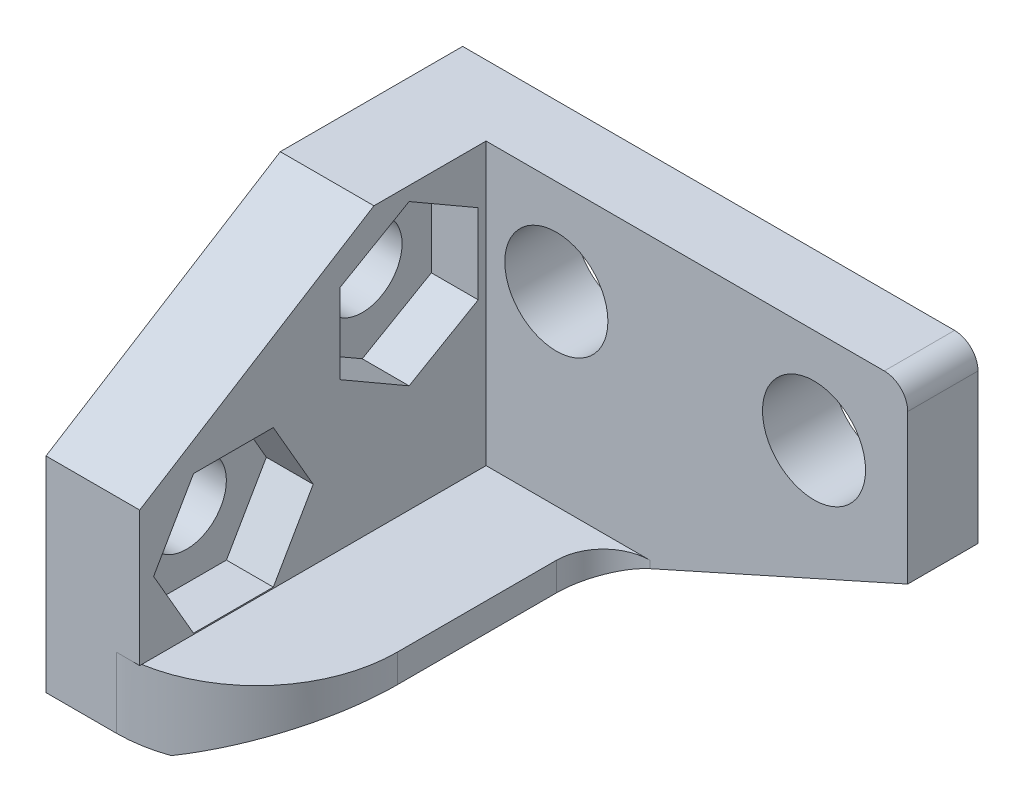
SolidWorks part; units mm, degrees
ref_plane "Спереди" through (0, 0, 0) normal (0, 0, 1) x (1, 0, 0)
ref_plane "Сверху" through (0, 0, 0) normal (0, 1, 0) x (1, 0, 0)
ref_plane "Справа" through (0, 0, 0) normal (1, 0, 0) x (0, 0, -1)
sketch "Эскиз1" plane through (0, 0, 0) normal (0, 0, 1) x (1, 0, 0)
  line L1 (-20, 25) -> (20, 25)
  line L2 (-20, 25) -> (-20, -25)
  line L3 (-20, -25) -> (20, -25)
  line L4 (20, 25) -> (20, -25)
  line L5 (-20, 25) -> (20, -25) construction
  line L6 (-20, -25) -> (20, 25) construction
  point P0 (0, 0)
  dimension "D1" = 50
  dimension "D2" = 40
extrude "Бобышка-Вытянуть1" add sketch "Эскиз1" along normal blind 5
sketch "Эскиз5" plane through (0, 0, 5) normal (0, 0, 1) x (1, 0, 0)
  line L0 (-20, 25) -> (-12.6319, 25)
  line L1 (-12.6319, 25) -> (-12.6319, 16.8645)
  line L2 (-12.6319, 16.8645) -> (13.9785, 16.8645)
  line L3 (13.9785, 16.8645) -> (14, 11)
  line L4 (14, 11) -> (-15, -2)
  line L5 (-15, -2) -> (-20, -2)
  line L6 (-20, -2) -> (-20, 25)
  line L7 (-12.6319, 25) -> (20, 25)
  line L8 (20, 25) -> (20, -25)
  line L9 (20, -25) -> (-20, -25)
  line L10 (-20, -25) -> (-20, -2)
  line M1 (20, -25) -> (20, 25)
  line M2 (20, 25) -> (-20, 25)
  line M3 (-20, 25) -> (-20, -25)
  line M4 (-20, -25) -> (20, -25)
extrude "Вырез-Вытянуть2" cut sketch "Эскиз5" against normal through all contours L4 L5 L1 L2 L3 M3 M4 M1 M2 region at (2.5012, -3.7526, 5)
fillet "Скругление2" radius 3 1 edges at (-12.6319, 16.8645, 2.5)
sketch "Эскиз6" plane through (0, 0, 5) normal (0, 0, 1) x (1, 0, 0)
  line L0 (-20, 25) -> (-17, 25)
  line L1 (-12.6319, 25) -> (-20, 25) construction
  line L2 (-17, 25) -> (-17, -2)
  line L3 (-15, -2) -> (-20, -2) construction
  line L4 (-17, -2) -> (-20, -2)
  line L5 (-20, -2) -> (-20, 25)
  line L6 (-17, -2) -> (-15, -2)
  line L7 (-15, -2) -> (-15, 1)
  line L8 (-15, 1) -> (-17, 1)
  line M4 (-12.6319, 25) -> (-20, 25)
  line M5 (-20, 25) -> (-20, -2)
  line M6 (-20, -2) -> (-15, -2)
  dimension "D1" = 3
  dimension "D2" = 3
extrude "Бобышка-Вытянуть2" add sketch "Эскиз6" along normal blind 10 contours L2 M4 M5 M6 | L7 L8 L2 M6 region at (-18.5, 11.5, 5) region at (-16, -0.5, 5)
sketch "Эскиз8" plane through (0, 0, 5) normal (0, 0, 1) x (1, 0, 0)
  line L0 (13.9785, 16.8645) -> (2.9785, 16.8645)
  line L1 (-9.6319, 16.8645) -> (13.9785, 16.8645) construction
  line L2 (2.9785, 16.8645) -> (2.9785, 6.0593)
  line L3 (14, 11) -> (-15, -2) construction
  line L4 (2.9785, 6.0593) -> (14, 11)
  line L5 (14, 11) -> (13.9785, 16.8645)
  dimension "D1" = 11
extrude "Вырез-Вытянуть3" cut sketch "Эскиз8" against normal through all
sketch "Эскиз9" plane through (0, 0, 5) normal (0, 0, 1) x (1, 0, 0)
  line L0 (-9.6319, 16.8645) -> (-20, 16.8645)
  line L1 (-20, 25) -> (-20, -2) construction
  line L2 (-20, 16.8645) -> (-20, 25)
  line L3 (-20, 25) -> (-9.6319, 25)
  line L4 (-9.6319, 25) -> (-9.6319, 16.8645)
extrude "Вырез-Вытянуть4" cut sketch "Эскиз9" against normal through all
sketch "Эскиз10" plane through (0, 0, 5) normal (0, 0, -1) x (-1, 0, 0)
  line L0 (17, 16.8645) -> (17, 25)
  line L1 (17, 25) -> (20, 25)
  line L2 (20, 25) -> (20, 16.8645)
  line L3 (20, 16.8645) -> (17, 16.8645)
  line L4 (17, 16.8645) -> (16.9146, 16.7365)
  line M1 (17, 16.8645) -> (20, 16.8645)
  line M2 (20, 16.8645) -> (20, 25)
  line M3 (20, 25) -> (17, 25)
  line M4 (17, 25) -> (17, 16.8645)
extrude "Вырез-Вытянуть5" cut sketch "Эскиз10" against normal through all contours M4 M1 M2 M3 region at (-18.5, 20.9323, 5)
fillet "Скругление3" radius 4 1 edges at (2.9785, 16.8645, 2.5)
fillet "Скругление4" radius 4 1 edges at (-15, -0.5, 5)
fillet "Скругление5" radius 4 1 edges at (-15, -0.5, 15)
sketch "Эскиз11" plane through (0, 0, 5) normal (0, 0, 1) x (1, 0, 0)
  line L0 (-17, 8.9323) -> (-21.0837, 8.9323) construction
  line L3 (-17, 16.8645) -> (-17, 1) construction
  line L4 (-21.0837, 8.9323) -> (5.5984, 8.9323) construction
  line L5 (-20, 8.9323) -> (-13, 8.9323)
  line L6 (-13, 8.9323) -> (-2, 8.9323)
  line L7 (-2, 8.9323) -> (2.879, 8.9323)
  circle A0 centre (-13, 8.9323) radius 2
  circle A1 centre (-2, 8.9323) radius 2
  dimension "D1" = 4
  dimension "D2" = 7
  dimension "D3" = 11
sketch "Эскиз12" plane through (-17, 0, 0) normal (1, 0, 0) x (0, 0, -1)
  line L0 (-9.7321, 16.8645) -> (-9.7321, 5.3907)
  line L1 (-14.4641, 16.8645) -> (-5, 16.8645) construction
  line L2 (-9.7321, 5.3907) -> (-15.9014, 5.3907)
  line L3 (-15.9014, 5.3907) -> (-15.9014, 16.8645)
  line L4 (-15.9014, 16.8645) -> (-9.7321, 16.8645)
extrude "Вырез-Вытянуть6" cut sketch "Эскиз12" against normal through all
sketch "Эскиз15" plane through (-20, 0, 0) normal (-1, 0, 0) x (0, 0, 1)
  line L0 (0, -2) -> (0, 13)
  line L1 (0, 16.8645) -> (0, -2) construction
  line L2 (0, 13) -> (9.7321, 13)
  line L3 (9.7321, 5.3907) -> (9.7321, 16.8645) construction
  line L4 (9.7321, 13) -> (9.7321, 16.8645)
  line L5 (9.7321, 16.8645) -> (0, 16.8645)
  line L6 (0, 16.8645) -> (0, 13)
  line M5 (9.7321, 5.3907) -> (9.7321, 16.8645)
  line M6 (9.7321, 16.8645) -> (0, 16.8645)
  line M7 (0, 16.8645) -> (0, -2)
  dimension "D1" = 15
extrude "Вырез-Вытянуть8" cut sketch "Эскиз15" against normal through all contours L2 M7 M5 M6 region at (-20, 14.9323, 4.866)
fillet "Скругление6" radius 8 1 edges at (-18.5, 5.3907, 9.7321)
fillet "Скругление7" radius 1 1 edges at (-18.5, 13, 9.7321)
sketch "Эскиз16" plane through (0, 0, 0) normal (0, 0, -1) x (-1, 0, 0)
  line L0 (20, 13) -> (-2, 13)
  line L1 (-2.9762, 13) -> (20, 13) construction
  line L2 (-2, 13) -> (-2, 2.1922)
  line L5 (0, 4.7241) -> (15, -2)
  line L7 (-2, 2.1922) -> (-7.7664, 2.1922)
  line L8 (-7.7664, 2.1922) -> (-7.7664, 13)
  line L9 (-7.7664, 13) -> (-2, 13)
  line M3 (20, 13) -> (-2.9762, 13)
  arc M4 (-2.9762, 13) -> (-2.9785, 12.8645) centre (1.0215, 12.8645) ccw
  line M5 (-2.9785, 12.8645) -> (-2.9785, 6.0593)
  line M6 (-2.9785, 6.0593) -> (15, -2)
  dimension "D1" = 22
extrude "Вырез-Вытянуть12" cut sketch "Эскиз16" against normal blind 10 contours L9 L8 L7 L2 M6 M5 M4 | L2 M3 M4 M5 M6 region at (2.4843, 9.4188, 0) region at (5.187, 7.3652, 0)
fillet "Скругление8" radius 1 1 edges at (2, 13, 2.5)
extrude "Вырез-Вытянуть13" cut sketch "Эскиз11" against normal blind 10 contours L5 A0 L6 | L6 A0 L5 | L6 A1 L7 | L7 A1 L6 region at (-13, 9.7811, 5) region at (-2, 9.7811, 5) region at (-2, 8.0834, 5) region at (-13, 8.0834, 5)
sketch "Эскиз18" plane through (-17, 0, 0) normal (1, 0, 0) x (0, 0, -1)
  line L0 (-5, 13) -> (-15.7866, 13)
  line L1 (-15.7866, 13) -> (-15.7866, -2)
  line L2 (-15.7866, -2) -> (-9, -2)
  line L3 (-11, -2) -> (-9, -2) construction
  line L4 (-5, 13) -> (-5, -2)
  line L5 (0, -2) -> (-9, -2) construction
  line L6 (-5, -2) -> (-9, -2)
extrude "Бобышка-Вытянуть3" add sketch "Эскиз18" against normal blind 3
sketch "Эскиз19" plane through (-17, 0, 0) normal (1, 0, 0) x (0, 0, -1)
  line L0 (-15.7866, 13) -> (-8.2866, 13)
  line L1 (-15.7866, 13) -> (-5, 13) construction
  line L2 (-8.2866, 13) -> (-8.2866, 9)
  line L4 (-8.2866, 5.8246) -> (-5.5366, 7.4123)
  line L5 (-5.5366, 7.4123) -> (-5.5366, 10.5877)
  line L6 (-5.5366, 10.5877) -> (-8.2866, 12.1754)
  line L7 (-8.2866, 12.1754) -> (-11.0366, 10.5877)
  line L8 (-11.0366, 10.5877) -> (-11.0366, 7.4123)
  line L9 (-11.0366, 7.4123) -> (-8.2866, 5.8246)
  circle A0 centre (-8.2866, 9) radius 2.75 construction
  dimension "D1" = 7.5
  dimension "D2" = 4
  dimension "D3" = 5.5
extrude "Вырез-Вытянуть14" cut sketch "Эскиз19" against normal blind 2.2 contours L8 L9 L4 L5 L6 L7 region at (-17, 6.6912, 9.6196)
sketch "Эскиз20" plane through (0, 0, 15.7866) normal (0, 0, 1) x (1, 0, 0)
  line L0 (-20, 13) -> (-17, 13)
  line L1 (-17, 13) -> (-17, -2)
  line L2 (-17, -2) -> (-20, -2)
  line L3 (-20, -2) -> (-20, 13)
extrude "Бобышка-Вытянуть5" add sketch "Эскиз20" along normal blind 4
sketch "Эскиз21" plane through (-17, 0, 0) normal (1, 0, 0) x (0, 0, -1)
  line L0 (-19.7866, -2) -> (-19.7866, 4)
  line L1 (-19.7866, -2) -> (-19.7866, 13) construction
  line L2 (-19.7866, 4) -> (-15.7866, 4)
  line L4 (-12.6112, 4) -> (-14.1989, 6.75)
  line L5 (-14.1989, 6.75) -> (-17.3743, 6.75)
  line L6 (-17.3743, 6.75) -> (-18.962, 4)
  line L7 (-18.962, 4) -> (-17.3743, 1.25)
  line L8 (-17.3743, 1.25) -> (-14.1989, 1.25)
  line L9 (-14.1989, 1.25) -> (-12.6112, 4)
  circle A0 centre (-15.7866, 4) radius 2.75 construction
  dimension "D1" = 6
  dimension "D2" = 4
  dimension "D3" = 5.5
extrude "Вырез-Вытянуть15" cut sketch "Эскиз21" against normal blind 2.2 contours L8 L9 L4 L5 L6 L7 region at (-17, 2.667, 13.4778)
sketch "Эскиз22" plane through (-17, 0, 0) normal (1, 0, 0) x (0, 0, -1)
  line L0 (-14.1989, 6.75) -> (-17.3743, 1.25)
  line L1 (-17.3743, 1.25) -> (-14.1989, 1.25)
  line L2 (-14.1989, 1.25) -> (-17.3743, 6.75)
  line L3 (-11.0366, 10.5877) -> (-5.5366, 7.4123)
  line L4 (-5.5366, 7.4123) -> (-5.5366, 10.5877)
  line L5 (-5.5366, 10.5877) -> (-11.0366, 7.4123)
  circle A0 centre (-15.7866, 4) radius 1.5
  circle A1 centre (-8.2866, 9) radius 1.5
  dimension "D1" = 3
  dimension "D2" = 3
extrude "Вырез-Вытянуть16" cut sketch "Эскиз22" against normal through all contours L2 A0 L0 | L0 A0 L2 | L2 A0 L0 | L0 A0 L2 | L5 A1 L3 | L3 A1 L5 | L5 A1 L3 | L3 A1 L5 region at (-17, 4, 14.9596) region at (-17, 4.9549, 15.7866) region at (-17, 3.0451, 15.7866) region at (-17, 4, 16.6136) region at (-17, 9.827, 8.2866) region at (-17, 9, 9.2415) region at (-17, 9, 7.3317) region at (-17, 8.173, 8.2866)
sketch "Эскиз23" plane through (0, 1, 0) normal (0, 1, 0) x (1, 0, 0)
  line L0 (-17, -5) -> (-17, -19.7866)
  line L1 (-17, -19.7866) -> (-11, -5)
  line L2 (-17, -5) -> (1, -5) construction
  line L3 (-11, -5) -> (-17, -5) construction
  line L4 (-11, -5) -> (-11, -19.7866)
  line L5 (-11, -19.7866) -> (-17, -19.7866)
  line M1 (-17, -5) -> (-17, -14.4641)
  arc M2 (-17, -14.4641) -> (-15, -11) centre (-19, -11) ccw
  line M3 (-15, -11) -> (-15, -9)
  arc M4 (-15, -9) -> (-11, -5) centre (-11, -9) cw
  line M5 (-11, -5) -> (-17, -5)
extrude "Бобышка-Вытянуть6" add sketch "Эскиз23" against normal up to surface (3 mm away) contours L5 L4 L1 | L0 L1 M4 M3 M2 | M5 M1 M2 M3 M4 region at (-15.7239, 1, 8.6966) region at (-14.3866, 1, 10.973) region at (-13, 1, 14.8577) up to face at (-16.9337, -2, 10.615)
sketch "Эскиз24" plane through (0, 0, 5) normal (0, 0, -1) x (-1, 0, 0)
  line L0 (15, -2) -> (11, -0.2069)
  line L1 (11, -0.2069) -> (11, -2)
  line L2 (11, -2) -> (15, -2)
extrude "Вырез-Вытянуть17" cut sketch "Эскиз24" against normal through all
fillet "Скругление9" radius 6 1 edges at (-11, 0.3966, 19.7866)
fillet "Скругление10" radius 2 1 edges at (-11, 0.3966, 5)
sketch "Эскиз25" plane through (0, 0, 0) normal (0, 0, -1) x (-1, 0, 0)
  line L1 (-2.731, 13.4239) -> (20.8767, 13.4239)
  line L2 (-2.731, 13.4239) -> (-2.731, -2.4603)
  line L3 (-2.731, -2.4603) -> (20.8767, -2.4603)
  line L4 (20.8767, 13.4239) -> (20.8767, -2.4603)
extrude "Вырез-Вытянуть18" cut sketch "Эскиз25" against normal blind 2
chamfer "Фаска1" distance 10 angle 32 1 edges at (-18.5, 13, 19.7866) first distance on face at (-12, 13, 8.9289)
sketch "Эскиз26" plane through (-17, 0, 0) normal (1, 0, 0) x (0, 0, -1)
  line L0 (-5, 1) -> (-5, 13)
  line L1 (-5, 13) -> (-9.7866, 13)
  line L2 (-9.7866, 13) -> (-19.7866, 6.7513)
  line L3 (-19.7866, 6.7513) -> (-19.7866, 1)
  line L4 (-19.7866, 1) -> (-5, 1)
  line L6 (-11.2366, 7.2968) -> (-8.2866, 5.5936)
  line L7 (-8.2866, 5.5936) -> (-5.3366, 7.2968)
  line L8 (-5.3366, 7.2968) -> (-5.3366, 10.7032)
  line L9 (-5.3366, 10.7032) -> (-8.2866, 12.4064)
  line L10 (-8.2866, 12.4064) -> (-11.2366, 10.7032)
  line L11 (-11.2366, 10.7032) -> (-11.2366, 7.2968)
  line L12 (-17.4898, 1.05) -> (-14.0834, 1.05)
  line L13 (-14.0834, 1.05) -> (-12.3802, 4)
  line L14 (-12.3802, 4) -> (-14.0834, 6.95)
  line L15 (-14.0834, 6.95) -> (-17.4898, 6.95)
  line L16 (-17.4898, 6.95) -> (-19.193, 4)
  line L17 (-19.193, 4) -> (-17.4898, 1.05)
  circle A0 centre (-8.2866, 9) radius 2.95 construction
  circle A1 centre (-15.7866, 4) radius 2.95 construction
  dimension "D1" = 5.9
  dimension "D2" = 5.9
extrude "Бобышка-Вытянуть7" add sketch "Эскиз26" along normal blind 1
sketch "Эскиз28" plane through (-19.2, 0, 0) normal (1, 0, 0) x (0, 0, -1)
  line L1 (-5.5366, 7.4123) -> (-5.5366, 10.5877)
  line L2 (-5.5366, 10.5877) -> (-8.2866, 12.1754)
  line L3 (-8.2866, 12.1754) -> (-11.0366, 10.5877)
  line L4 (-11.0366, 10.5877) -> (-11.0366, 7.4123)
  line L5 (-11.0366, 7.4123) -> (-8.2866, 5.8246)
  line L6 (-8.2866, 5.8246) -> (-5.5366, 7.4123)
  line L7 (-12.6112, 4) -> (-14.1989, 6.75)
  line L8 (-14.1989, 6.75) -> (-17.3743, 6.75)
  line L9 (-17.3743, 6.75) -> (-18.962, 4)
  line L10 (-18.962, 4) -> (-17.3743, 1.25)
  line L11 (-17.3743, 1.25) -> (-14.1989, 1.25)
  line L12 (-14.1989, 1.25) -> (-12.6112, 4)
  circle A0 centre (-8.2866, 9) radius 1.5
  circle A1 centre (-15.7866, 4) radius 1.5
  circle A2 centre (-8.2866, 9) radius 2.75 construction
  circle A3 centre (-15.7866, 4) radius 2.75 construction
extrude "Бобышка-Вытянуть8" add sketch "Эскиз28" along normal blind 2
sketch "Эскиз30" plane through (-16, 0, 0) normal (1, 0, 0) x (0, 0, -1)
  line L1 (-11.2366, 7.2968) -> (-8.2866, 5.5936)
  line L2 (-8.2866, 5.5936) -> (-5.3366, 7.2968)
  line L3 (-5.3366, 7.2968) -> (-5.3366, 10.7032)
  line L4 (-5.3366, 10.7032) -> (-8.2866, 12.4064)
  line L5 (-8.2866, 12.4064) -> (-11.2366, 10.7032)
  line L6 (-11.2366, 10.7032) -> (-11.2366, 7.2968)
  line L7 (-19.193, 4) -> (-17.4898, 1.05)
  line L8 (-17.4898, 1.05) -> (-14.0834, 1.05)
  line L9 (-14.0834, 1.05) -> (-12.3802, 4)
  line L10 (-12.3802, 4) -> (-14.0834, 6.95)
  line L11 (-14.0834, 6.95) -> (-17.4898, 6.95)
  line L12 (-17.4898, 6.95) -> (-19.193, 4)
  circle A0 centre (-8.2866, 9) radius 2.95 construction
  circle A1 centre (-15.7866, 4) radius 2.95 construction
extrude "Вырез-Вытянуть20" cut sketch "Эскиз30" against normal blind 2
sketch "Эскиз31" plane through (-20, 0, 0) normal (-1, 0, 0) x (0, 0, 1)
  circle A0 centre (8.2866, 9) radius 1.7
  circle A1 centre (15.7866, 4) radius 1.7
  dimension "D1" = 3.4
extrude "Вырез-Вытянуть21" cut sketch "Эскиз31" against normal through all
sketch "Эскиз32" plane through (0, 0, 2) normal (0, 0, -1) x (-1, 0, 0)
  circle A0 centre (2, 8.9323) radius 2.2
  circle A1 centre (13, 8.9323) radius 2.2
  dimension "D1" = 4.4
extrude "Вырез-Вытянуть22" cut sketch "Эскиз32" against normal through all
